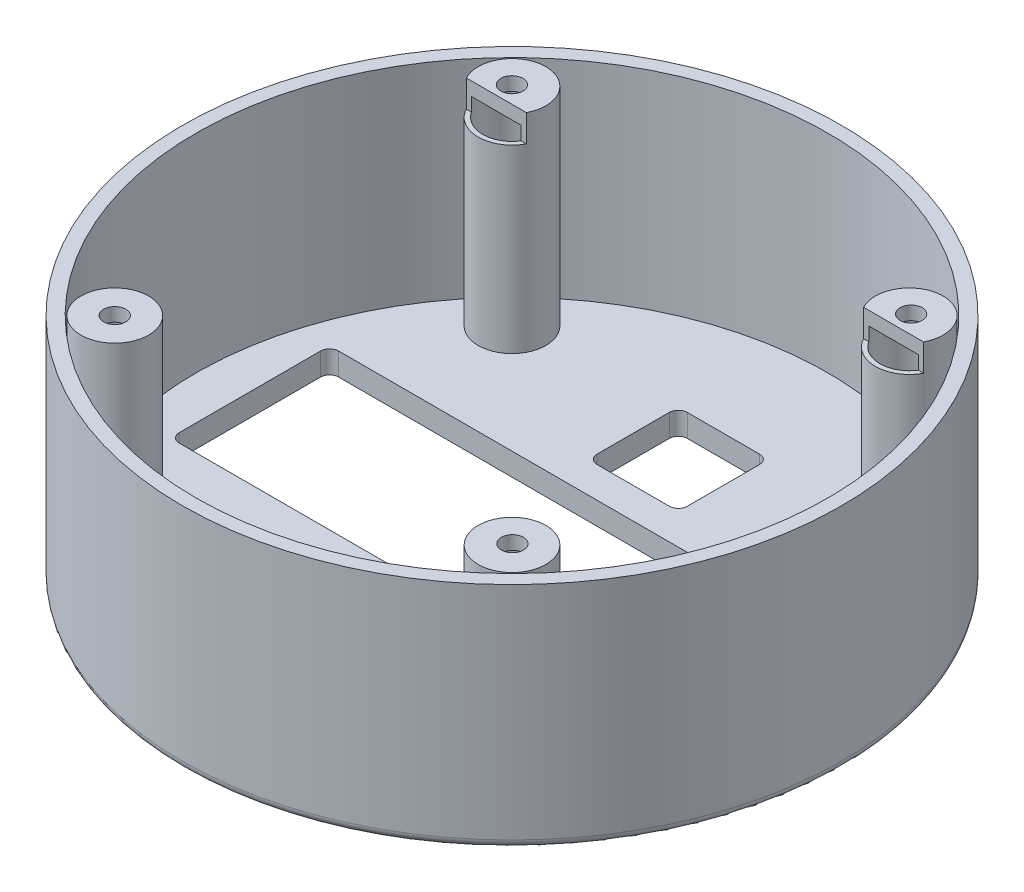
SolidWorks part; units mm, degrees
ref_plane "Front Plane" through (0, 0, 0) normal (0, 0, 1) x (1, 0, 0)
ref_plane "Top Plane" through (0, 0, 0) normal (0, 1, 0) x (1, 0, 0)
ref_plane "Right Plane" through (0, 0, 0) normal (1, 0, 0) x (0, 0, -1)
sketch "Sketch2" plane through (0, 0, 0) normal (0, 1, 0) x (1, 0, 0)
  circle A0 centre (0, 0) radius 36.5
extrude "Boss-Extrude1" add sketch "Sketch2" along normal blind 2.5
sketch "Sketch3" plane through (0, 2.5, 0) normal (0, 1, 0) x (1, 0, 0)
  circle A0 centre (0, 0) radius 36.5
  circle A1 centre (0, 0) radius 35
extrude "Boss-Extrude2" add sketch "Sketch3" along normal blind 35
sketch "Sketch4" plane through (0, 2.5, 0) normal (0, 1, 0) x (1, 0, 0)
  line L7 (-22, 22) -> (22, -22) construction
  line L8 (-22, -22) -> (22, 22) construction
  circle A0 centre (-22, 22) radius 3.75
  circle A1 centre (22, 22) radius 3.75
  circle A2 centre (22, -22) radius 3.75
  circle A3 centre (-22, -22) radius 3.75
extrude "Boss-Extrude3" add sketch "Sketch4" along normal blind 35
sketch "Sketch5" plane through (0, 37.5, 0) normal (0, 1, 0) x (1, 0, 0)
  line L5 (22, -22) -> (-22, 22) construction
  line L6 (22, 22) -> (-22, -22) construction
  circle A0 centre (-22, -22) radius 1.225
  circle A1 centre (-22.145, 22.1354) radius 1.225
  circle A2 centre (21.9598, 22.2466) radius 1.225
  circle A3 centre (21.9042, -21.8582) radius 1.225
  point P0 (0, 0)
extrude "Cut-Extrude2" cut sketch "Sketch5" against normal through all
sketch "Sketch9" plane through (0, 0, 0) normal (0, -1, 0) x (1, 0, 0)
  line L1 (-22, 22) -> (22, 22)
  line L2 (-22, 22) -> (-22, -22)
  line L3 (-22, -22) -> (22, -22)
  line L4 (22, 22) -> (22, -22)
  line L5 (-22, 22) -> (22, -22) construction
  line L6 (-22, -22) -> (22, 22) construction
  circle A0 centre (22, 22) radius 3.25
  circle A1 centre (22, -22) radius 3.25
  circle A2 centre (-22, -22) radius 3.25
  circle A3 centre (-22, 22) radius 3.25
  point P0 (0, 0)
  circle M1 centre (-22.145, -22.1354) radius 1.225
  circle M2 centre (21.9598, -22.2466) radius 1.225
  circle M3 centre (21.9042, 21.8582) radius 1.225
  circle M4 centre (-22, 22) radius 1.225
extrude "Cut-Extrude7" cut sketch "Sketch9" against normal blind 24 contours L4 A0 L1 M3 | L1 A0 L4 M3 | L3 A1 L4 M2 | L4 A1 L3 M2 | L2 A2 L3 M1 | L1 A3 L2 M4 | L2 A3 L1 M4 | L3 A2 L2 M1 region at (-22.9312, 0, 22.9312) region at (-20.4783, 0, 20.4783) region at (22, 0, 25.1581) region at (20.4459, 0, 20.4499) region at (-20.5126, 0, -20.513) region at (-22.0919, 0, -19.8345) region at (24.2331, 0, -19.7669) region at (20.5123, 0, -20.5004)
fillet "Fillet2" radius 0.75 1 edges at (0, 37.5, 35)
sketch "Sketch17" plane through (0, 0, 0) normal (0, -1, 0) x (1, 0, 0)
  line L1 (-5, -23.419) -> (5, -23.419)
  line L2 (-5, -23.419) -> (-5, -13.419)
  line L3 (-5, -13.419) -> (5, -13.419)
  line L4 (5, -23.419) -> (5, -13.419)
  line L5 (-5, -23.419) -> (5, -13.419) construction
  line L6 (-5, -13.419) -> (5, -23.419) construction
  point P0 (0, -18.419)
extrude "Cut-Extrude9" cut sketch "Sketch17" against normal blind 10
sketch "Sketch19" plane through (0, 0, 0) normal (0, -1, 0) x (1, 0, 0)
  line L8 (30.2475, -9.9947) -> (-30.201, -9.9947)
  line L9 (30.2475, -9.9947) -> (30.2475, 7.6653)
  line L10 (30.2475, 7.6653) -> (-30.201, 7.6653)
  line L11 (-30.201, -9.9947) -> (-30.201, 7.6653)
  line L12 (30.2475, -9.9947) -> (-30.201, 7.6653) construction
  line L13 (30.2475, 7.6653) -> (-30.201, -9.9947) construction
extrude "Cut-Extrude10" cut sketch "Sketch19" against normal blind 10
fillet "Fillet8" radius 1 2 edges at (5, 1.25, -23.419) (30.2475, 1.25, -9.9947)
fillet "Fillet9" radius 1 2 edges at (-5, 1.25, -13.419) (-30.201, 1.25, 7.6653)
fillet "Fillet10" radius 1 2 edges at (5, 1.25, -13.419) (30.2475, 1.25, 7.6653)
fillet "Fillet11" radius 1 2 edges at (-30.201, 1.25, -9.9947) (-5, 1.25, -23.419)
fillet "Fillet7" radius 1 1 edges at (0, 0, 36.5)
sketch "Sketch20" plane through (0, 37.5, 0) normal (0, 1, 0) x (1, 0, 0)
  circle A0 centre (0, 0) radius 36.5
extrude "Cut-Extrude11" cut sketch "Sketch20" against normal blind 12
sketch "Sketch21" plane through (0, 25.5, 0) normal (0, 1, 0) x (1, 0, 0)
  line L0 (25.322, 20.2601) -> (-25.322, 20.2601)
  line L1 (-25.322, 20.2601) -> (-25.322, 17.7047)
  line L2 (-25.322, 17.7047) -> (25.322, 17.7047)
  line L3 (25.322, 17.7047) -> (25.322, 20.2601)
  circle A0 centre (22, 22) radius 3.75 construction
  circle A1 centre (-22, 22) radius 3.75 construction
  point P7 (0, 0)
extrude "Cut-Extrude13" cut sketch "Sketch21" against normal blind 3
